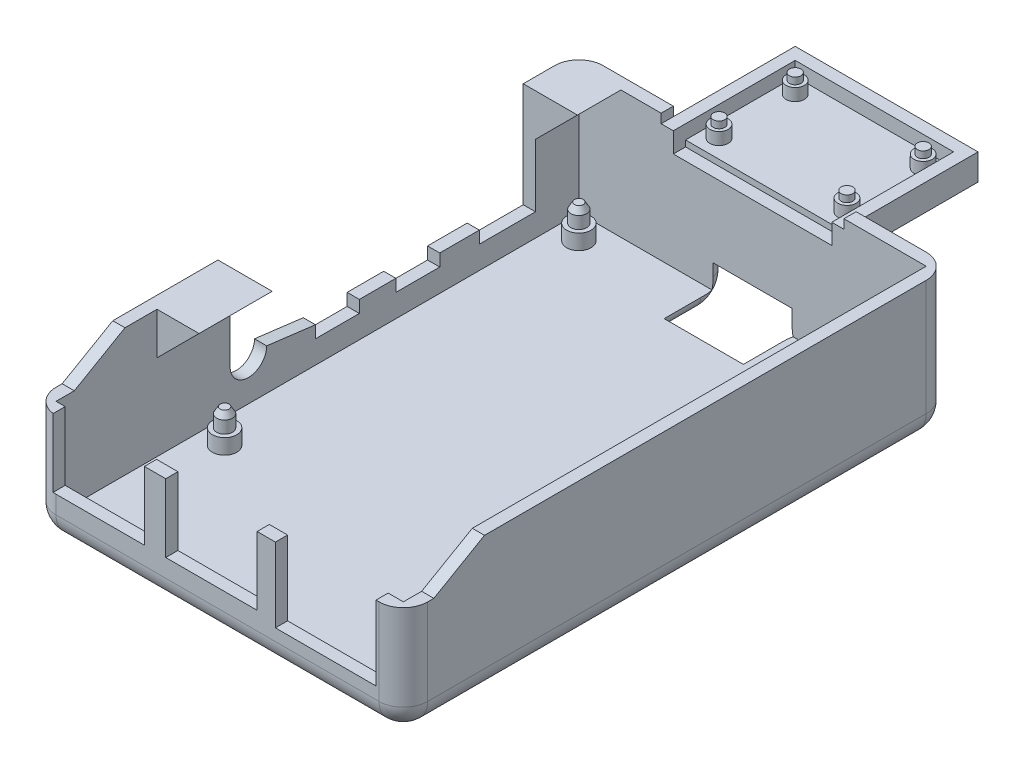
SolidWorks part; units mm, degrees
ref_plane "Płaszczyzna przednia" through (0, 0, 0) normal (0, 0, 1) x (1, 0, 0)
ref_plane "Płaszczyzna górna" through (0, 0, 0) normal (0, 1, 0) x (1, 0, 0)
ref_plane "Płaszczyzna prawa" through (0, 0, 0) normal (1, 0, 0) x (0, 0, -1)
sketch "Szkic1" plane through (0, 0, 0) normal (0, 1, 0) x (1, 0, 0)
  line L1 (-30.5, 44.9) -> (30.5, 44.9)
  line L2 (-30.5, 44.9) -> (-30.5, -44.9)
  line L3 (-30.5, -44.9) -> (30.5, -44.9)
  line L4 (30.5, 44.9) -> (30.5, -44.9)
  line L5 (-30.5, 44.9) -> (30.5, -44.9) construction
  line L6 (-30.5, -44.9) -> (30.5, 44.9) construction
  point P0 (0, 0)
  dimension "D1" = 61
  dimension "D2" = 89.8
extrude "Dodanie-wyciągnięcie1" add sketch "Szkic1" along normal blind 2
sketch "Szkic2" plane through (0, 2, 0) normal (0, 1, 0) x (1, 0, 0)
  line L0 (28.5, -42.9) -> (28.5, 42.9)
  line L1 (28.5, 42.9) -> (-28.5, 42.9)
  line L2 (-28.5, 42.9) -> (-28.5, -42.9)
  line L3 (-28.5, -42.9) -> (28.5, -42.9)
  line L4 (30.5, -44.9) -> (30.5, 44.9)
  line L5 (30.5, 44.9) -> (-30.5, 44.9)
  line L6 (-30.5, 44.9) -> (-30.5, -44.9)
  line L7 (-30.5, -44.9) -> (30.5, -44.9)
  line L8 (30.5, -44.9) -> (30.5, 44.9)
  line L9 (30.5, 44.9) -> (-30.5, 44.9)
  line L10 (-30.5, 44.9) -> (-30.5, -44.9)
  line L11 (-30.5, -44.9) -> (30.5, -44.9)
  dimension "D1" = 0
  dimension "D2" = 2
extrude "Dodanie-wyciągnięcie2" add sketch "Szkic2" along normal blind 16.15
sketch "Szkic3" plane through (0, 0, 44.9) normal (0, 0, 1) x (1, 0, 0)
  line L0 (-30.5, 18.15) -> (30.5, 18.15) construction
  line L1 (-27, 18.15) -> (-12, 18.15)
  line L2 (-27, 18.15) -> (-27, 6.95)
  line L3 (-27, 6.95) -> (-12, 6.95)
  line L4 (-12, 18.15) -> (-12, 6.95)
  line L5 (-30.5, 18.15) -> (-30.5, 0) construction
  line L6 (-8.5, 18.15) -> (6.5, 18.15)
  line L7 (-8.5, 18.15) -> (-8.5, 6.95)
  line L8 (-8.5, 6.95) -> (6.5, 6.95)
  line L9 (6.5, 18.15) -> (6.5, 6.95)
  line L10 (26, 18.15) -> (9.5, 18.15)
  line L11 (26, 18.15) -> (26, 5.95)
  line L12 (26, 5.95) -> (9.5, 5.95)
  line L13 (9.5, 18.15) -> (9.5, 5.95)
  dimension "D1" = 3.5
  dimension "D2" = 15
  dimension "D3" = 3.5
  dimension "D4" = 16.5
  dimension "D5" = 3
  dimension "D6" = 11.2
  dimension "D7" = 12.2
extrude "Wytnij-wyciągnięcie1" cut sketch "Szkic3" against normal up to surface (2 mm away) up to face at (0, 10.075, 42.9)
sketch "Szkic4" plane through (0, 0, -44.9) normal (0, 0, -1) x (-1, 0, 0)
  line L0 (-30.5, 0) -> (30.5, 0) construction
  line L1 (-6.5, 0) -> (6.5, 0)
  line L2 (-6.5, 0) -> (-6.5, 5.95)
  line L3 (-6.5, 5.95) -> (6.5, 5.95)
  line L4 (6.5, 0) -> (6.5, 5.95)
  line L5 (-6.5, 5.95) -> (-30.5, 5.95)
  line L7 (-30.5, 18.15) -> (-30.5, 0) construction
  line L8 (6.5, 5.95) -> (30.5, 5.95)
  line L9 (30.5, 18.15) -> (30.5, 0) construction
  dimension "D1" = 13
  dimension "D2" = 5.95
extrude "Wytnij-wyciągnięcie2" cut sketch "Szkic4" against normal blind 10 contours L2 L1 L4 L3
sketch "Szkic6" plane through (-30.5, 0, 0) normal (-1, 0, 0) x (0, 0, 1)
  line L0 (-35.77, 18.15) -> (14.33, 18.15)
  line L1 (-35.77, 18.15) -> (-35.77, 5.75)
  line L2 (-35.77, 5.75) -> (14.33, 5.75)
  line L3 (14.33, 18.15) -> (14.33, 5.75)
  line L4 (-26.57, 5.75) -> (-26.57, 7.75)
  line L5 (-26.57, 7.75) -> (-20.07, 7.75)
  line L6 (-20.07, 7.75) -> (-20.07, 5.75)
  line L7 (-12.87, 5.75) -> (-12.87, 7.75)
  line L8 (-12.87, 7.75) -> (-6.87, 7.75)
  line L9 (-6.87, 7.75) -> (-6.87, 5.75)
  line L10 (0.33, 5.75) -> (0.33, 7.75)
  line L11 (0.33, 7.75) -> (8.33, 8.75)
  line L12 (8.33, 8.75) -> (8.33, 5.75)
  line L13 (-6.87, 7.75) -> (0.33, 7.75) construction
  line L14 (-12.87, 7.75) -> (-20.07, 7.75) construction
  line L15 (-44.9, 18.15) -> (44.9, 18.15) construction
  line L16 (-44.9, 0) -> (44.9, 0) construction
  line L17 (-44.9, 18.15) -> (-44.9, 0) construction
  circle A0 centre (11.33, 8.75) radius 3
  line M7 (44.9, 18.15) -> (-44.9, 18.15)
  dimension "D2" = 6
  dimension "D1" = 50.1
  dimension "D3" = 9.2
  dimension "D4" = 7.2
  dimension "D5" = 6.5
  dimension "D6" = 6
  dimension "D7" = 2
  dimension "D8" = 5.75
  dimension "D9" = 9.13
extrude "Wytnij-wyciągnięcie4" cut sketch "Szkic6" against normal up to surface (2 mm away) contours A0 L3 L1 L2 L4 L5 L6 L7 L8 L9 L10 L11 M7 | A0 region at (-30.5, 12.5758, -12.3031) region at (-30.5, 8.75, 11.33) up to face at (-28.5, 10.075, 0)
sketch "Szkic7" plane through (0, 2, 0) normal (0, 1, 0) x (1, 0, 0)
  line L0 (24.57, 38.97) -> (24.57, -19.17) construction
  line L1 (24.57, -19.17) -> (-24.57, -19.17) construction
  line L2 (-24.57, -19.17) -> (-24.57, 38.97) construction
  line L3 (-24.57, 38.97) -> (24.57, 38.97) construction
  line L4 (0, 38.97) -> (0, -19.17) construction
  line L5 (-24.57, 9.9) -> (24.57, 9.9) construction
  line L7 (28.5, -42.9) -> (28.5, 42.9) construction
  line L8 (28.5, 42.9) -> (6.5, 42.9) construction
  line L9 (-28.5, 42.9) -> (-28.5, -42.9) construction
  line L10 (-28.5, -42.9) -> (28.5, -42.9) construction
  circle A0 centre (24.57, -19.17) radius 2
  circle A1 centre (-24.57, -19.17) radius 2
  circle A2 centre (24.57, 38.97) radius 2
  circle A3 centre (-24.57, 38.97) radius 2
  point P12 (0, 9.9)
  dimension "D1" = 4
  dimension "D2" = 3.93
  dimension "D5" = 23.73
  dimension "D3" = 3.93
  dimension "D4" = 3.93
extrude "Dodanie-wyciągnięcie3" add sketch "Szkic7" along normal blind 2.5
ref_plane "haczyki-przednia" through (0, 0, -9.9) normal (0, 0, 1) x (1, 0, 0)
ref_plane "haczyki-prawa" through (0, 0, 0) normal (-1, 0, 0) x (0, 0, 1)
sketch "Szkic8" plane through (0, 4.5, 0) normal (0, 1, 0) x (1, 0, 0)
  circle A0 centre (-24.57, 38.97) radius 1.3
  dimension "D1" = 2.6
extrude "Dodanie-wyciągnięcie4" add sketch "Szkic8" along normal blind 2
sketch "Szkic9" plane through (0, 6.5, 0) normal (0, 1, 0) x (1, 0, 0)
  circle A1 centre (-24.57, 38.97) radius 1.3
  circle A2 centre (-24.57, 38.97) radius 1.3
  dimension "D1" = 0
extrude "Dodanie-wyciągnięcie5" add sketch "Szkic9" along normal blind 1 draft 30
mirror "Lustro1" about plane through (0, 0, 0) normal (-1, 0, 0) of "Dodanie-wyciągnięcie5", "Dodanie-wyciągnięcie4"
mirror "Lustro2" about plane through (0, 0, -9.9) normal (0, 0, 1) of "Lustro1"
sketch "Szkic11" plane through (0, 18.15, 0) normal (0, 1, 0) x (1, 0, 0)
  line L0 (-28.5, 35.77) -> (-30.5, 35.77)
  line L1 (-30.5, 35.77) -> (-30.5, 44.9)
  line L2 (-30.5, 44.9) -> (-20.5, 44.9)
  line L3 (30.5, 44.9) -> (-30.5, 44.9) construction
  line L4 (-20.5, 44.9) -> (-20.5, 42.9)
  line L5 (28.5, 42.9) -> (-28.5, 42.9) construction
  line L6 (-20.5, 42.9) -> (-28.5, 42.9)
  line L7 (-28.5, 42.9) -> (-28.5, 35.77)
  line L8 (-30.5, -14.33) -> (-28.5, -14.33)
  line L9 (-28.5, -14.33) -> (-28.5, -44.9)
  line L10 (-30.5, -44.9) -> (-27, -44.9) construction
  line L11 (-28.5, -44.9) -> (-30.5, -44.9)
  line L12 (-30.5, -44.9) -> (-30.5, -14.33)
  dimension "D1" = 10
extrude "Dodanie-wyciągnięcie6" add sketch "Szkic11" along normal blind 4.8
sketch "Szkic12" plane through (-30.5, 0, 0) normal (-1, 0, 0) x (0, 0, 1)
  line L5 (44.9, 18.15) -> (39.9, 18.15)
  line L6 (44.9, 22.95) -> (44.9, 0) construction
  line L7 (39.9, 18.15) -> (31.5862, 22.95)
  line L8 (14.33, 22.95) -> (44.9, 22.95) construction
  line L9 (31.5862, 22.95) -> (44.9, 22.95)
  line L10 (44.9, 22.95) -> (44.9, 18.15)
  line L11 (44.9, 18.15) -> (42.9, 18.15) construction
  dimension "D1" = 30
  dimension "D2" = 5
extrude "Wytnij-wyciągnięcie5" cut sketch "Szkic12" against normal up to surface (2 mm away) up to face at (-28.5, 10.469, -3.6595)
sketch "Szkic13" plane through (0, 0, 14.33) normal (0, 0, -1) x (-1, 0, 0)
  line L0 (28.5, 22.95) -> (21.6, 22.95)
  line L1 (21.6, 22.95) -> (28.5, 16.05)
  line L2 (28.5, 22.95) -> (28.5, 8.75) construction
  line L3 (28.5, 16.05) -> (28.5, 22.95)
  dimension "D1" = 45
  dimension "D2" = 6.9
extrude "Dodanie-wyciągnięcie7" add sketch "Szkic13" against normal blind 12
sketch "Szkic14" plane through (0, 0, -35.77) normal (0, 0, 1) x (1, 0, 0)
  line L0 (-21.6, 22.95) -> (-28.5, 22.95)
  line L1 (-28.5, 22.95) -> (-28.5, 16.05)
  line L5 (-21.6, 22.95) -> (-30.5, 22.95)
  line L6 (-28.5, 16.05) -> (-21.6, 22.95)
  line L7 (-28.5, 8.75) -> (-28.5, 16.05)
  line L8 (-30.5, 8.75) -> (-28.5, 8.75)
  line L9 (-30.5, 22.95) -> (-30.5, 8.75)
  line L11 (-28.5, 16.05) -> (-21.6, 22.95)
  dimension "D1" = 0
extrude "Dodanie-wyciągnięcie8" add sketch "Szkic14" against normal up to surface (7.13 mm away) up to face at (-4.1, 10.21, -42.9)
sketch "Szkic15" plane through (-30.5, 0, 0) normal (-1, 0, 0) x (0, 0, 1)
  line L0 (14.33, 22.95) -> (31.5862, 22.95) construction
  line L1 (-39.9, 21.95) -> (-36.77, 21.95)
  line L2 (-39.9, 21.95) -> (-39.9, 17.05)
  line L3 (-39.9, 17.05) -> (-36.77, 17.05)
  line L4 (-36.77, 21.95) -> (-36.77, 17.05)
  line L5 (15.33, 21.95) -> (25.33, 21.95)
  line L6 (15.33, 21.95) -> (15.33, 17.05)
  line L7 (15.33, 17.05) -> (25.33, 17.05)
  line L8 (25.33, 21.95) -> (25.33, 17.05)
  line L9 (-44.9, 22.95) -> (-44.9, 0) construction
  line L10 (14.33, 22.95) -> (14.33, 8.75) construction
  line L11 (26.33, 16.05) -> (14.33, 16.05) construction
  line L12 (26.33, 16.05) -> (26.33, 22.95) construction
  line L15 (-35.77, 22.95) -> (-35.77, 5.75) construction
  dimension "D1" = 1
  dimension "D2" = 1
  dimension "D3" = 1
  dimension "D4" = 1
  dimension "D5" = 1
  dimension "D6" = 5
extrude "Wytnij-wyciągnięcie6" cut sketch "Szkic15" against normal up to surface (7.9 mm away) up to face at (-25.05, 19.5, -39.335)
sketch "Szkic16" plane through (0, 0, -39.9) normal (0, 0, 1) x (1, 0, 0)
  line L0 (-27.5, 17.05) -> (-22.6, 21.95)
  line L1 (-22.6, 21.95) -> (-24.0142, 21.95)
  line L2 (-22.6, 21.95) -> (-30.5, 21.95) construction
  line L3 (-24.0142, 21.95) -> (-28.9142, 17.05)
  line L4 (-27.5, 17.05) -> (-30.5, 17.05) construction
  line L5 (-28.9142, 17.05) -> (-27.5, 17.05)
  dimension "D1" = 1
extrude "Dodanie-wyciągnięcie9" add sketch "Szkic16" along normal up to surface (3.13 mm away) up to face at (-27.775, 19.5, -36.77)
sketch "Szkic17" plane through (0, 0, 25.33) normal (0, 0, -1) x (-1, 0, 0)
  line L0 (27.5, 17.05) -> (28.9142, 17.05)
  line L1 (27.5, 17.05) -> (30.5, 17.05) construction
  line L2 (28.9142, 17.05) -> (24.0142, 21.95)
  line L3 (22.6, 21.95) -> (30.5, 21.95) construction
  line L4 (24.0142, 21.95) -> (22.6, 21.95)
  line L5 (22.6, 21.95) -> (27.5, 17.05)
  dimension "D1" = 1
extrude "Dodanie-wyciągnięcie10" add sketch "Szkic17" along normal up to surface (10 mm away) up to face at (-27.775, 19.5, 15.33)
fillet "Zaokrąglenie1" radius 4 9 edges at (-18.5, 0, -44.9) (18.5, 0, -44.9) (30.5, 0, 0) (0, 0, 44.9) (-30.5, 0, 0) (-30.5, 9.075, 44.9) (30.5, 9.075, 44.9) (30.5, 9.075, -44.9) (-30.5, 11.475, -44.9)
fillet "Zaokrąglenie2" radius 2 8 edges at (-6.5, 4.975, -44.9) (-6.5, 1.1716, -43.7284) (6.5, 4.975, -44.9) (6.5, 1.1716, -43.7284) (0, 5.95, -44.9) (-6.5, 0, -37.9) (6.5, 0, -37.9) (0, 0, -34.9)
sketch "Szkic19" plane through (0, 18.15, 0) normal (0, 1, 0) x (1, 0, 0)
  line L0 (30.5, -31.5862) -> (28.5, -31.5862)
  line L1 (-28.5, -31.5862) -> (-30.5, -31.5862) construction
  line L8 (26, -44.9) -> (26.5, -44.9)
  line L9 (30.5, -40.9) -> (30.5, 40.9)
  line L10 (26.5, 44.9) -> (-20.5, 44.9)
  line L11 (-20.5, 44.9) -> (-20.5, 42.9)
  line L12 (-20.5, 42.9) -> (28.5, 42.9)
  line L13 (28.5, 42.9) -> (28.5, -42.9)
  line L14 (28.5, -42.9) -> (26, -42.9)
  line L15 (26, -42.9) -> (26, -44.9)
  line L16 (26, -44.9) -> (26.5, -44.9)
  line L17 (30.5, -40.9) -> (30.5, 40.9)
  line L18 (26.5, 44.9) -> (-20.5, 44.9)
  line L19 (-20.5, 44.9) -> (-20.5, 42.9)
  line L20 (-20.5, 42.9) -> (28.5, 42.9)
  line L21 (28.5, 42.9) -> (28.5, -42.9)
  line L22 (28.5, -42.9) -> (26, -42.9)
  line L23 (26, -42.9) -> (26, -44.9)
  arc A2 (26.5, -44.9) -> (30.5, -40.9) centre (26.5, -40.9) ccw
  arc A3 (30.5, 40.9) -> (26.5, 44.9) centre (26.5, 40.9) ccw
  arc A4 (26.5, -44.9) -> (30.5, -40.9) centre (26.5, -40.9) ccw
  arc A5 (30.5, 40.9) -> (26.5, 44.9) centre (26.5, 40.9) ccw
  point P12 (-29.5, -31.5862)
  line M14 (30.5, -40.9) -> (30.5, 40.9)
  arc M15 (30.5, 40.9) -> (26.5, 44.9) centre (26.5, 40.9) ccw
  line M16 (26.5, 44.9) -> (-20.5, 44.9)
  line M17 (-20.5, 44.9) -> (-20.5, 42.9)
  line M18 (-20.5, 42.9) -> (28.5, 42.9)
  line M19 (28.5, 42.9) -> (28.5, -42.9)
  dimension "D1" = 0
extrude "Dodanie-wyciągnięcie11" add sketch "Szkic19" along normal up to surface (4.8 mm away) contours L0 M14 M15 M16 M17 M18 M19 region at (29.5, 18.15, 30.6669) up to face at (-26.8667, 22.95, 24.0821)
sketch "Szkic20" plane through (30.5, 0, 0) normal (1, 0, 0) x (0, 0, -1)
  line L0 (-39.9, 18.15) -> (-31.5862, 18.15)
  line L1 (-31.5862, 18.15) -> (-31.5862, 22.95)
  line L22 (42.9, 16.05) -> (35.77, 16.05)
  line L23 (35.77, 16.05) -> (35.77, 5.75)
  line L24 (35.77, 5.75) -> (26.57, 5.75)
  line L25 (26.57, 5.75) -> (26.57, 7.75)
  line L26 (26.57, 7.75) -> (20.07, 7.75)
  line L27 (20.07, 7.75) -> (20.07, 5.75)
  line L28 (20.07, 5.75) -> (12.87, 5.75)
  line L29 (12.87, 5.75) -> (12.87, 7.75)
  line L30 (12.87, 7.75) -> (6.87, 7.75)
  line L31 (6.87, 7.75) -> (6.87, 5.75)
  line L32 (6.87, 5.75) -> (-0.33, 5.75)
  line L33 (-0.33, 5.75) -> (-0.33, 7.75)
  line L34 (-0.33, 7.75) -> (-8.33, 8.75)
  line L35 (-14.33, 8.75) -> (-14.33, 16.05)
  line L36 (-14.33, 16.05) -> (-26.33, 16.05)
  line L37 (-26.33, 16.05) -> (-26.33, 22.95)
  line L38 (-26.33, 22.95) -> (-31.5862, 22.95)
  line L39 (-31.5862, 22.95) -> (-39.9, 18.15)
  line L40 (-39.9, 18.15) -> (-42.9, 18.15)
  line L41 (-42.9, 18.15) -> (-42.9, 2)
  line L42 (-42.9, 2) -> (42.9, 2)
  line L43 (42.9, 2) -> (42.9, 16.05)
  line L44 (42.9, 16.05) -> (35.77, 16.05)
  line L45 (35.77, 16.05) -> (35.77, 5.75)
  line L46 (35.77, 5.75) -> (26.57, 5.75)
  line L47 (26.57, 5.75) -> (26.57, 7.75)
  line L48 (26.57, 7.75) -> (20.07, 7.75)
  line L49 (20.07, 7.75) -> (20.07, 5.75)
  line L50 (20.07, 5.75) -> (12.87, 5.75)
  line L51 (12.87, 5.75) -> (12.87, 7.75)
  line L52 (12.87, 7.75) -> (6.87, 7.75)
  line L53 (6.87, 7.75) -> (6.87, 5.75)
  line L54 (6.87, 5.75) -> (-0.33, 5.75)
  line L55 (-0.33, 5.75) -> (-0.33, 7.75)
  line L56 (-0.33, 7.75) -> (-8.33, 8.75)
  line L57 (-14.33, 8.75) -> (-14.33, 16.05)
  line L58 (-14.33, 16.05) -> (-26.33, 16.05)
  line L59 (-26.33, 16.05) -> (-26.33, 22.95)
  line L60 (-26.33, 22.95) -> (-31.5862, 22.95)
  line L61 (-31.5862, 22.95) -> (-39.9, 18.15)
  line L62 (-39.9, 18.15) -> (-42.9, 18.15)
  line L63 (-42.9, 18.15) -> (-42.9, 2)
  line L64 (-42.9, 2) -> (42.9, 2)
  line L65 (42.9, 2) -> (42.9, 16.05)
  arc A1 (-14.33, 8.75) -> (-8.33, 8.75) centre (-11.33, 8.75) ccw
  arc A2 (-14.33, 8.75) -> (-8.33, 8.75) centre (-11.33, 8.75) ccw
  line M24 (-31.5862, 18.15) -> (-40.9, 18.15)
  line M29 (-31.5862, 22.95) -> (-31.5862, 18.15)
  dimension "D1" = 0
extrude "Dodanie-wyciągnięcie12" add sketch "Szkic20" against normal up to surface (2 mm away) contours L61 M29 M24 region at (30.5, 19.75, 34.3574) up to face at (28.5, 14.3667, 10.5287)
sketch "Szkic18" plane through (0, 0, -44.9) normal (0, 0, -1) x (-1, 0, 0)
  line L12 (-15, 22.95) -> (-15, 21.45)
  line L17 (-26.5, 22.95) -> (26.5, 22.95) construction
  line L18 (-15, 21.45) -> (-13, 21.45)
  line L19 (-13, 21.45) -> (-13, 18.15)
  line L20 (-13, 18.15) -> (13, 18.15)
  line L21 (13, 18.15) -> (13, 21.45)
  line L22 (13, 21.45) -> (15, 21.45)
  line L23 (15, 21.45) -> (15, 22.95)
  line L24 (15, 22.95) -> (-15, 22.95)
  line L25 (-13, 18.15) -> (-30.5, 18.15) construction
  line L26 (-30.5, 4) -> (-30.5, 22.95) construction
  line L27 (13, 18.15) -> (30.5, 18.15) construction
  line L28 (30.5, 22.95) -> (30.5, 4) construction
  dimension "D1" = 1.5
  dimension "D2" = 2
  dimension "D3" = 3.3
  dimension "D4" = 26
extrude "Wytnij-wyciągnięcie7" cut sketch "Szkic18" against normal up to surface (2 mm away) up to face at (-1.9643, 8.2748, -42.9)
sketch "Szkic21" plane through (0, 0, -44.9) normal (0, 0, -1) x (-1, 0, 0)
  line L0 (-15, 21.45) -> (-13, 21.45)
  line L1 (-13, 21.45) -> (-13, 19.15)
  line L2 (-13, 21.45) -> (-13, 18.15) construction
  line L3 (-13, 19.15) -> (13, 19.15)
  line L4 (13, 18.15) -> (13, 21.45) construction
  line L5 (13, 19.15) -> (13, 21.45)
  line L6 (13, 21.45) -> (15, 21.45)
  line L7 (15, 21.45) -> (15, 17.15)
  line L8 (15, 17.15) -> (-15, 17.15)
  line L9 (-15, 17.15) -> (-15, 21.45)
  line L10 (0, 17.15) -> (0, 18.15) construction
  line L11 (-13, 18.15) -> (13, 18.15) construction
  line L12 (0, 18.15) -> (0, 19.15) construction
  dimension "D1" = 2
extrude "Dodanie-wyciągnięcie13" add sketch "Szkic21" along normal blind 20
sketch "Szkic22" plane through (0, 19.15, 0) normal (0, 1, 0) x (1, 0, 0)
  line L0 (13, 64.9) -> (-13, 64.9)
  line L1 (-13, 64.9) -> (-13, 62.9)
  line L2 (-13, 64.9) -> (-13, 44.9) construction
  line L3 (-13, 62.9) -> (13, 62.9)
  line L4 (13, 42.9) -> (13, 64.9) construction
  line L5 (13, 62.9) -> (13, 64.9)
  line L6 (13, 64.9) -> (15, 64.9) construction
extrude "Dodanie-wyciągnięcie14" add sketch "Szkic22" along normal up to surface (2.3 mm away) up to face at (14.2, 21.45, -52.1)
sketch "Szkic23" plane through (0, 19.15, 0) normal (0, 1, 0) x (1, 0, 0)
  line L0 (-10.5, 60.4) -> (10.5, 60.4) construction
  line L1 (10.5, 60.4) -> (10.5, 47.9) construction
  line L2 (10.5, 47.9) -> (-10.5, 47.9) construction
  line L3 (-10.5, 47.9) -> (-10.5, 60.4) construction
  line L4 (0, 60.4) -> (0, 47.9) construction
  line L5 (10.5, 54.15) -> (-10.5, 54.15) construction
  line L6 (10.5, 54.15) -> (13, 54.15) construction
  line L8 (-10.5, 54.15) -> (-13, 54.15) construction
  line L10 (13, 62.9) -> (13, 44.9) construction
  line L11 (-13, 62.9) -> (13, 62.9) construction
  line L12 (-13, 62.9) -> (-13, 44.9) construction
  circle A0 centre (10.5, 47.9) radius 1.5
  circle A1 centre (-10.5, 47.9) radius 1.5
  circle A2 centre (-10.5, 60.4) radius 1.5
  circle A3 centre (10.5, 60.4) radius 1.5
  point P12 (0, 54.15)
  dimension "D1" = 3
  dimension "D2" = 2.5
  dimension "D3" = 2.5
  dimension "D4" = 12.5
extrude "Dodanie-wyciągnięcie15" add sketch "Szkic23" along normal blind 2
ref_plane "cam przednia" through (0, 0, -54.15) normal (0, 0, -1) x (-1, 0, 0)
ref_plane "cam prawa" through (0, 0, 0) normal (-1, 0, 0) x (0, 0, 1)
sketch "Szkic24" plane through (0, 21.15, 0) normal (0, 1, 0) x (1, 0, 0)
  circle A0 centre (-10.5, 60.4) radius 0.95
  dimension "D1" = 1.9
extrude "Dodanie-wyciągnięcie16" add sketch "Szkic24" along normal blind 1.1
mirror "Lustro3" about plane through (0, 0, 0) normal (-1, 0, 0) of "Dodanie-wyciągnięcie16"
mirror "Lustro4" about plane through (0, 0, -54.15) normal (0, 0, -1) of "Lustro3"
